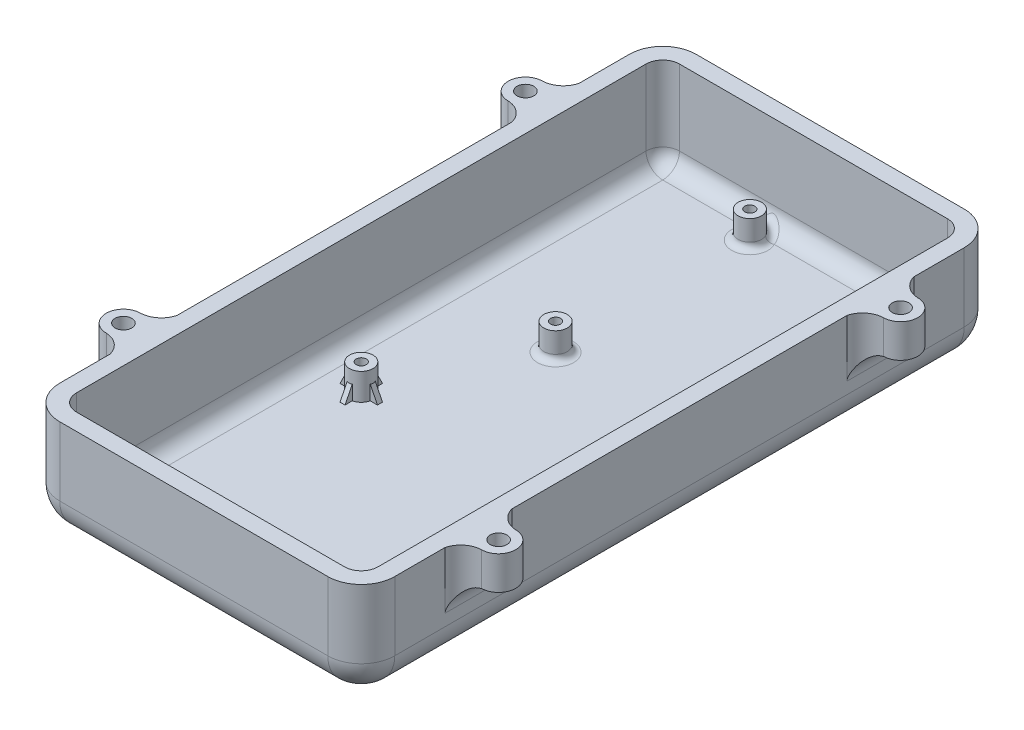
SolidWorks part; units mm, degrees
ref_plane "前视基准面" through (0, 0, 0) normal (0, 0, 1) x (1, 0, 0)
ref_plane "上视基准面" through (0, 0, 0) normal (0, 1, 0) x (1, 0, 0)
ref_plane "右视基准面" through (0, 0, 0) normal (1, 0, 0) x (0, 0, -1)
sketch "Sketch1" plane through (0, 0, 0) normal (0, 1, 0) x (1, 0, 0)
  line L0 (-50, -95) -> (-50, 95)
  line L1 (-45, -90) -> (45, -90)
  line L2 (-45, -90) -> (-45, 90)
  line L3 (-45, 90) -> (45, 90)
  line L4 (45, -90) -> (45, 90)
  line L5 (-45, -90) -> (45, 90) construction
  line L6 (-45, 90) -> (45, -90) construction
  line L7 (-50, 95) -> (50, 95)
  line L8 (50, -95) -> (50, 95)
  line L9 (-50, -95) -> (50, -95)
  point P0 (0, 0)
  dimension "D1" = 90
  dimension "D2" = 180
  dimension "D3" = 5
extrude "Boss-Extrude1" add sketch "Sketch1" along normal blind 27.5
sketch3d "3DSketch1"
  line L4 (50, 0, 95) -> (-50, 0, 95)
  line L5 (-50, 0, 95) -> (-50, 0, -95)
  line L6 (-50, 0, -95) -> (50, 0, -95)
  line L7 (50, 0, -95) -> (50, 0, 95)
  line L8 (50, 0, 95) -> (-50, 0, 95)
  line L9 (-50, 0, 95) -> (-50, 0, -95)
  line L10 (-50, 0, -95) -> (50, 0, -95)
  line L11 (50, 0, -95) -> (50, 0, 95)
  dimension "D1" = 0
extrude "Boss-Extrude2" add sketch "3DSketch1" along direction (0, 1, 0) on the side of the normal blind 3
fillet "Fillet3" radius 10 4 edges
fillet "Fillet4" radius 10 8 edges at (-47.0711, -3, 92.0711) (47.0711, -3, 92.0711) (47.0711, -3, -92.0711) (-47.0711, -3, -92.0711)
fillet "Fillet5" radius 5 4 edges at (45, 13.75, 90) (45, 13.75, -90) (-45, 13.75, -90) (-45, 13.75, 90)
fillet "Fillet6" radius 5 8 edges at (-43.5355, 0, 88.5355) (-45, 0, 0) (-43.5355, 0, -88.5355) (0, 0, -90) (43.5355, 0, -88.5355) (45, 0, 0) (43.5355, 0, 88.5355) (0, 0, 90)
sketch "Sketch2" plane through (0, 27.5, 0) normal (0, 1, 0) x (1, 0, 0)
  line L0 (-50, 0) -> (-50, 60) construction
  line L1 (-50, 85) -> (-50, -85) construction
  line L2 (-50, 60) -> (-56, 60) construction
  line L4 (-56, 60) -> (-61.5, 60) construction
  line L5 (0, 0) -> (0, 13.0765) construction
  line L6 (0, 0) -> (12.355, 0) construction
  line L10 (-50, 50) -> (-50, 70)
  line L11 (50, 50) -> (50, 70)
  line L12 (50, -50) -> (50, -70)
  line L13 (-50, -50) -> (-50, -70)
  arc A0 (-56, 65.1284) -> (-56, 54.8716) centre (-56, 60) ccw
  circle A4 centre (-56, 60) radius 2.5
  arc A17 (-56, 65.1284) -> (-50, 70) centre (-56.2944, 71.6217) ccw
  arc A18 (-56, 54.8716) -> (-50, 50) centre (-56.2944, 48.3783) cw
  circle A19 centre (56, 60) radius 2.5
  arc A20 (56, 54.8716) -> (50, 50) centre (56.2944, 48.3783) ccw
  arc A21 (56, 65.1284) -> (56, 54.8716) centre (56, 60) cw
  arc A22 (56, 65.1284) -> (50, 70) centre (56.2944, 71.6217) cw
  circle A23 centre (56, -60) radius 2.5
  arc A24 (56, -65.1284) -> (56, -54.8716) centre (56, -60) ccw
  arc A25 (56, -65.1284) -> (50, -70) centre (56.2944, -71.6217) ccw
  arc A26 (56, -54.8716) -> (50, -50) centre (56.2944, -48.3783) cw
  circle A27 centre (-56, -60) radius 2.5
  arc A28 (-56, -54.8716) -> (-50, -50) centre (-56.2944, -48.3783) ccw
  arc A29 (-56, -65.1284) -> (-56, -54.8716) centre (-56, -60) cw
  arc A30 (-56, -65.1284) -> (-50, -70) centre (-56.2944, -71.6217) cw
  dimension "D1" = 6
  dimension "D3" = 5
  dimension "D2" = 60
  dimension "D4" = 10
extrude "Boss-Extrude3" add sketch "Sketch2" against normal blind 10
fillet "Fillet7" radius 7 4 edges at (-50, 17.5, -60) (50, 17.5, -60) (50, 17.5, 60) (-50, 17.5, 60)
sketch "Sketch3" plane through (0, 17.5, 0) normal (0, -1, 0) x (1, 0, 0)
  circle A0 centre (-56, -60) radius 5.1284
  circle A1 centre (-56, 60) radius 5.1284
  circle A2 centre (56, 60) radius 5.1284
  circle A3 centre (56, -60) radius 5.1284
extrude "Cut-Extrude1" cut sketch "Sketch3" along normal blind 10
sketch "Sketch5" plane through (0, 0, 0) normal (0, 1, 0) x (1, 0, 0)
  line L0 (0, 0) -> (0, -45) construction
  line L1 (0, -45) -> (20.9359, -45) construction
  line L2 (30, -15) -> (-30, -15) construction
  line L3 (30, -15) -> (30, -75) construction
  line L4 (30, -75) -> (-30, -75) construction
  line L5 (-30, -15) -> (-30, -75) construction
  line L6 (30, -15) -> (-30, -75) construction
  line L7 (30, -75) -> (-30, -15) construction
  circle A0 centre (30, -75) radius 3.5
  circle A1 centre (30, -75) radius 1.5
  circle A2 centre (-30, -75) radius 1.5
  circle A3 centre (-30, -75) radius 3.5
  circle A4 centre (-30, -15) radius 1.5
  circle A5 centre (-30, -15) radius 3.5
  circle A6 centre (30, -15) radius 1.5
  circle A7 centre (30, -15) radius 3.5
  dimension "D4" = 7
  dimension "D5" = 3
  dimension "D1" = 45
  dimension "D2" = 60
  dimension "D3" = 60
extrude "Boss-Extrude4" add sketch "Sketch5" along normal blind 8
ref_plane "Plane4" through (0, 0, 75) normal (0, 0, -1) x (-1, 0, 0)
sketch "Sketch13" plane through (0, 0, 75) normal (0, 0, -1) x (-1, 0, 0)
  line L0 (-27.4095, 0) -> (-27.4095, 6)
  line L1 (-27.4095, 0) -> (-24.4095, 0)
  line L2 (-24.4095, 0) -> (-27.4095, 6)
  dimension "D1" = 6
  dimension "D2" = 3
extrude "Boss-Extrude6" add sketch "Sketch13" along normal mid plane 1.5
pattern_circular "CirPattern1" count 4 over 360 about axis through (30, 8, 75) along (0, -1, 0) of "Boss-Extrude6"
sketch "Sketch14" plane through (0, 0, 0) normal (0, 1, 0) x (1, 0, 0)
  line L0 (0, 0) -> (0, -85) construction
  line L1 (-40, -85) -> (40, -85) construction
ref_plane "Plane5" through (0, 0, 0) normal (1, 0, 0) x (0, 0, -1)
mirror "Mirror1" about plane through (0, 0, 0) normal (1, 0, 0) of "CirPattern1", "Boss-Extrude6"
sketch "Sketch15" plane through (0, 0, 0) normal (0, 1, 0) x (1, 0, 0)
  line L0 (-30, -75) -> (-30, -15) construction
  line L1 (-30, -45) -> (5.5244, -45) construction
ref_plane "Plane6" through (0, 0, 45) normal (0, 0, -1) x (-1, 0, 0)
mirror "Mirror2" about plane through (0, 0, 45) normal (0, 0, -1) of "Mirror1", "CirPattern1"
sketch "Sketch17" plane through (0, 0, 0) normal (0, 1, 0) x (1, 0, 0)
  circle A0 centre (37.5, 24.5) radius 1.5
  circle A1 centre (37.5, 24.5) radius 3.5
  circle A2 centre (-11.5, 24.5) radius 1.5
  circle A3 centre (-11.5, 24.5) radius 3.5
  circle A4 centre (37.5, 82.5) radius 1.5
  circle A5 centre (37.5, 82.5) radius 3.5
  circle A6 centre (-11.5, 82.5) radius 1.5
  circle A7 centre (-11.5, 82.5) radius 3.5
  dimension "D1" = 3
  dimension "D2" = 7
  dimension "D3" = 7
  dimension "D4" = 3
  dimension "D5" = 7
  dimension "D6" = 3
  dimension "D7" = 7
  dimension "D8" = 3
extrude "Boss-Extrude7" add sketch "Sketch17" along normal blind 8
fillet "Fillet9" radius 1.9 9 edges at (-10.5227, 0.0747, -85.8608) (37.8662, 0.0971, -85.9808) (39.9749, 0, -84.9749) (40.8608, 0.0747, -81.5227) (40.9808, 0.0971, -24.1338) (-11.5, 0, -79) (35.0251, 0, -80.0251) (34, 0, -24.5) (-11.5, 0, -21)
